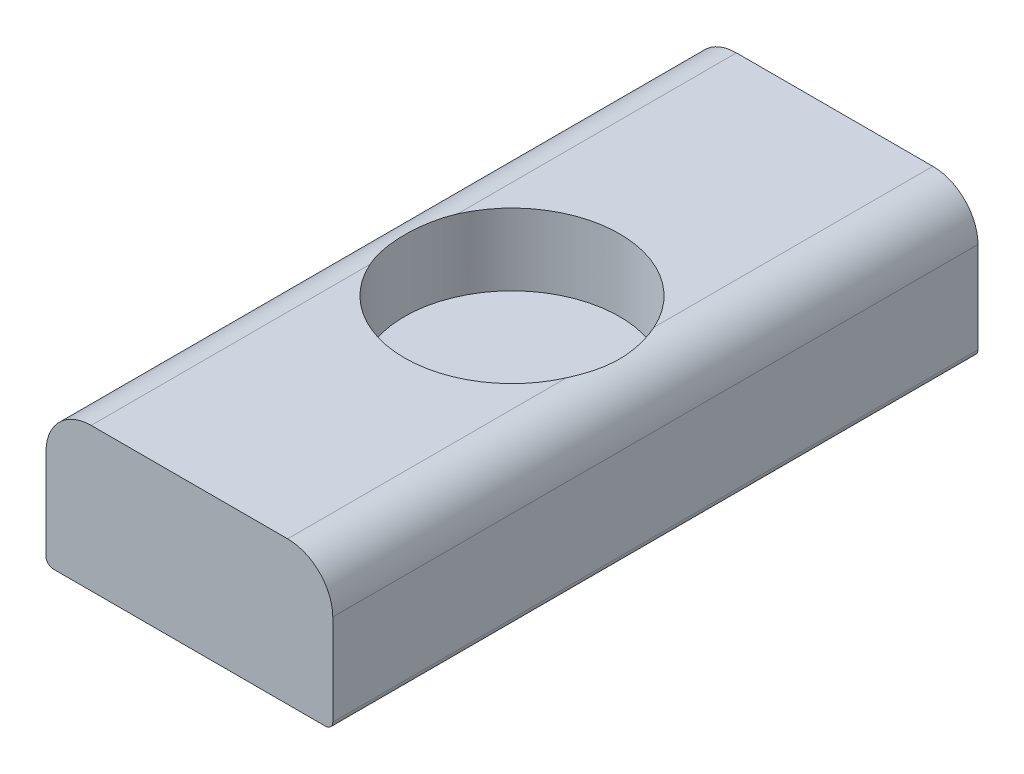
SolidWorks part; units mm, degrees
ref_plane "Front" through (0, 0, 0) normal (0, 0, 1) x (1, 0, 0)
ref_plane "Top" through (0, 0, 0) normal (0, 1, 0) x (1, 0, 0)
ref_plane "Right" through (0, 0, 0) normal (1, 0, 0) x (0, 0, -1)
sketch "Sketch1" plane through (0, 0, 0) normal (0, 0, 1) x (1, 0, 0)
  line L1 (-20, -10) -> (20, -10)
  line L2 (-20, -10) -> (-20, 10)
  line L3 (-20, 10) -> (20, 10)
  line L4 (20, -10) -> (20, 10)
  line L5 (-20, -10) -> (20, 10) construction
  line L6 (-20, 10) -> (20, -10) construction
  point P0 (0, 0)
  dimension "D1" = 40
  dimension "D2" = 20
extrude "Boss-Extrude1" add sketch "Sketch1" along normal blind 90
fillet "Fillet1" radius 1 2 edges at (-20, -10, 45) (20, -10, 45)
sketch "Sketch2" plane through (0, 10, 0) normal (0, 1, 0) x (1, 0, 0)
  line L0 (20, 0) -> (-20, 0) construction
  circle A0 centre (0, -45) radius 15
  dimension "D2" = 30
  dimension "D1" = 45
extrude "Cut-Extrude1" cut sketch "Sketch2" against normal blind 10
fillet "Fillet2" radius 6.3 2 edges at (20, 10, 45) (-20, 10, 45)
